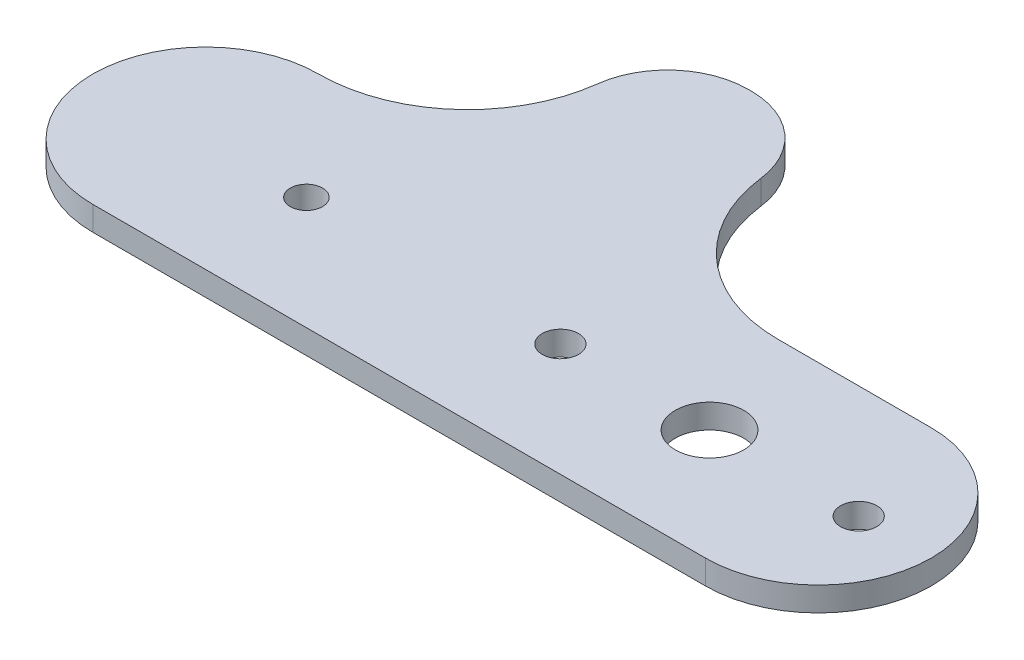
SolidWorks part; units mm, degrees
ref_plane "前视" through (0, 0, 0) normal (0, 0, 1) x (1, 0, 0)
ref_plane "上视" through (0, 0, 0) normal (0, 1, 0) x (1, 0, 0)
ref_plane "右视" through (0, 0, 0) normal (1, 0, 0) x (0, 0, -1)
sketch "草图1" plane through (0, 0, 0) normal (0, 1, 0) x (1, 0, 0)
  line L1 (-45, 14) -> (45, 14)
  line L2 (-45, 14) -> (-45, -14)
  line L3 (-45, -14) -> (45, -14)
  line L4 (45, 14) -> (45, -14)
  line L5 (-45, 14) -> (45, -14) construction
  line L6 (-45, -14) -> (45, 14) construction
  circle A0 centre (17.5, 0) radius 4.25
  circle A1 centre (-32.5, 0) radius 2
  point P0 (0, 0)
  dimension "D3" = 4
  dimension "D4" = 8.5
  dimension "D1" = 90
  dimension "D2" = 77.5
  dimension "28" = 28
  dimension "D5" = 50
extrude "凸台-拉伸1" add sketch "草图1" along normal blind 3
sketch "草图2" plane through (0, 3, 0) normal (0, 1, 0) x (1, 0, 0)
  text T0 "             <b>2</b>"
extrude "凸台-拉伸2" [suppressed] add sketch "草图2" along normal blind 0.5
sketch "草图3" plane through (0, 3, 0) normal (0, 1, 0) x (1, 0, 0)
  circle A0 centre (36, 0) radius 2.25
  circle A1 centre (-1, 0) radius 2.25
  point P4 (17.5, 0)
  dimension "D3" = 4.5
  dimension "D4" = 4.5
  dimension "D1" = 37
  dimension "D2" = 18.5
extrude "切除-拉伸1" cut sketch "草图3" against normal up to next
sketch "草图4" plane through (0, 3, 0) normal (0, 1, 0) x (1, 0, 0)
  line L1 (-26.5, 14) -> (-6.5, 14)
  line L2 (-26.5, 14) -> (-26.5, 39)
  line L3 (-26.5, 39) -> (-6.5, 39)
  line L4 (-6.5, 14) -> (-6.5, 39)
  line L5 (45, 14) -> (-45, 14) construction
  line L6 (-45, 14) -> (-45, -14) construction
  dimension "D1" = 25
  dimension "D2" = 20
  dimension "D3" = 18.5
extrude "凸台-拉伸3" add sketch "草图4" against normal blind 3
fillet "圆角6" radius 18.5 2 edges
fillet "圆角9" radius 10 2 edges at (-6.5, 1.5, -39) (-26.5, 1.5, -39)
sketch "草图6" plane through (0, 3, 0) normal (0, 1, 0) x (1, 0, 0)
  line L0 (-45, 14) -> (-45, -14) construction
  line L1 (-45, -14) -> (-45, 14)
  arc A0 (-45, 14) -> (-45, -14) centre (-45, 0) ccw
extrude "凸台-拉伸4" add sketch "草图6" against normal blind 3 contours A0 L1
fillet "圆角11" 2 edges at (45, 1.5, 14) (45, 1.5, -14) type full round first side face at (0, 1.5, 14) second side face at (36.75, 1.5, -14) middle face at (45, 1.5, 0)
